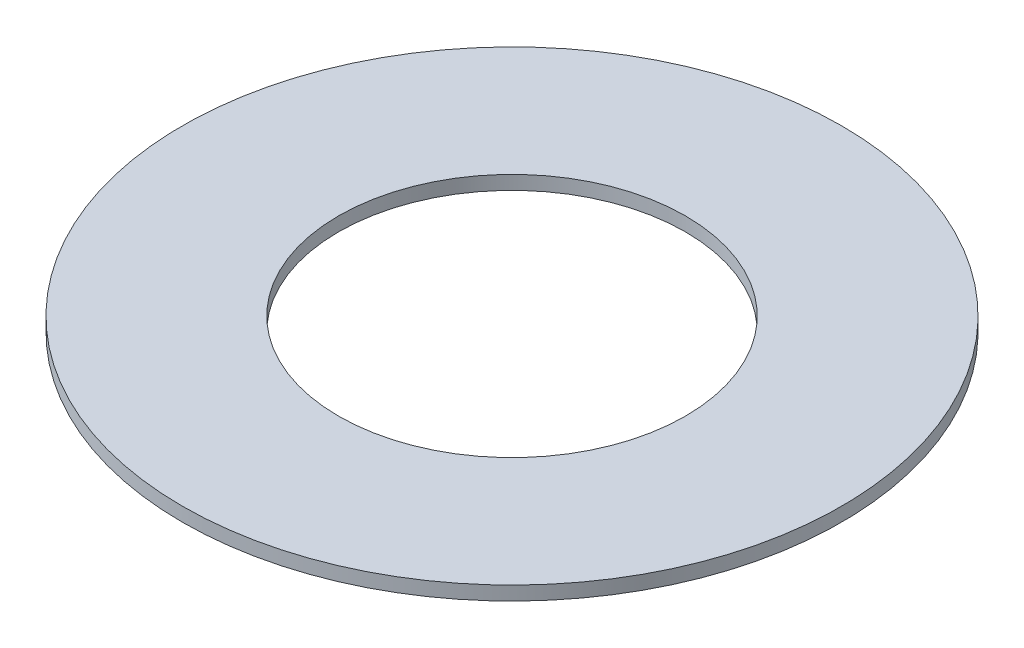
SolidWorks part; units mm, degrees
ref_plane "Front Plane" through (0, 0, 0) normal (0, 0, 1) x (1, 0, 0)
ref_plane "Top Plane" through (0, 0, 0) normal (0, 1, 0) x (1, 0, 0)
ref_plane "Right Plane" through (0, 0, 0) normal (1, 0, 0) x (0, 0, -1)
sketch "Sketch1" plane through (0, 0, 0) normal (0, 1, 0) x (1, 0, 0)
  circle A0 centre (0, 0) radius 95
  dimension "FLANGE_OD" = 190
extrude "Boss-Extrude1" add sketch "Sketch1" along normal blind 4
sketch "Sketch2" plane through (0, 0, 0) normal (0, 1, 0) x (1, 0, 0)
  circle A0 centre (0, 0) radius 50
  dimension "BORE_D" = 100
extrude "Cut-Extrude1" cut sketch "Sketch2" along normal through all
sketch "Sketch3" plane through (0, 4, 0) normal (0, 1, 0) x (1, 0, 0)
  circle A0 centre (0, 0) radius 43.2325 construction
  circle A1 centre (-43.2325, 0) radius 5.8873
  dimension "BOLT_D" = 11.7746
  dimension "BOLT_PCD" = 86.465
extrude "Cut-Extrude2" cut sketch "Sketch3" against normal blind 2.8482 rebuild error yes
pattern_circular "CirPattern1" count 4 over 360 rebuild error yes
